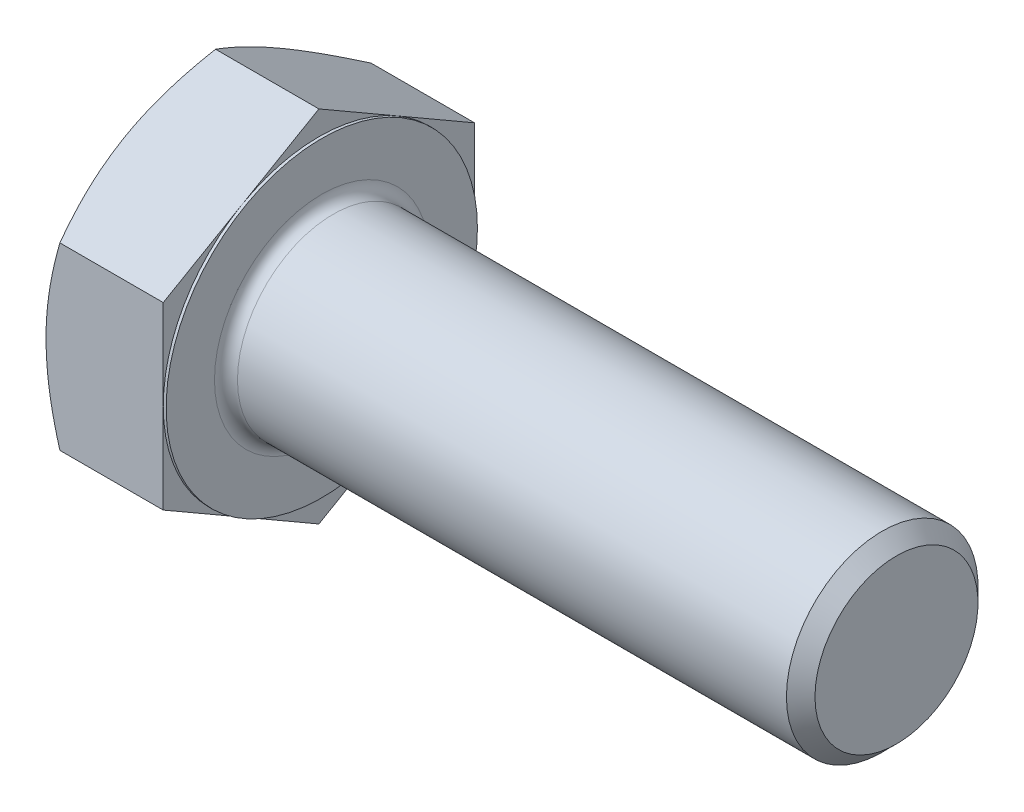
SolidWorks part; units mm, degrees
extrude "BaseHead" add sketch "Sketch1" along normal blind 15.9258
sketch "Sketch1" plane through (0, 0, 0) normal (1, 0, 0) x (0, 0, -1)
  line L0 (20.6375, 11.9151) -> (20.6375, -11.9151)
  line L1 (-20.6375, 11.9151) -> (-20.6375, -11.9151)
  line L2 (20.6375, -11.9151) -> (0, -23.8301)
  line L3 (0, -23.8301) -> (-20.6375, -11.9151)
  line L4 (20.6375, 11.9151) -> (0, 23.8301)
  line L5 (0, 23.8301) -> (-20.6375, 11.9151)
  dimension "D2" = 120
  dimension "D3" = 20.6375
  dimension "D4" = 20.6375
  dimension "D5" = 20.6375
revolve "HeadChamfer" cut sketch "Sketch3" angle 360 about L6 other way angle 60
sketch "Sketch3" plane through (0, 0, 0) normal (0, 0, 1) x (1, 0, 0)
  line L0 (0, 20.6375) -> (5.5094, 30.1801)
  line L1 (0, 23.8301) -> (0, 11.9151) construction
  line L2 (5.5094, 30.1801) -> (5.5094, 36.5301)
  line L3 (5.5094, 36.5301) -> (-12.7, 36.5301)
  line L4 (-12.7, 36.5301) -> (-12.7, 20.6375)
  line L5 (-12.7, 20.6375) -> (0, 20.6375)
  line L6 (0, 0) -> (99.06, 0) construction
  line L7 (15.9258, 23.8301) -> (0, 23.8301) construction
  dimension "D1" = 20.6375
  dimension "D2" = 6.35
  dimension "D3" = 12.7
  dimension "D4" = 6.35
  dimension "Head_ch_ang" = 30
ref_plane "Plane1" through (0, 0, 0) normal (0, 0, 1) x (1, 0, 0)
ref_plane "Plane2" through (0, 0, 0) normal (0, 1, 0) x (1, 0, 0)
ref_plane "Plane3" through (0, 0, 0) normal (1, 0, 0) x (0, 0, -1)
sketch "BodySke" plane through (0, 0, 0) normal (0, 0, 1) x (1, 0, 0)
  line L0 (0, 11.9151) -> (0, -11.9151) construction
  line L1 (0, 0) -> (92.1258, 0)
  line L2 (0, 0) -> (0, 12.7)
  line L3 (0, 12.7) -> (90.2335, 12.7)
  line L4 (92.1258, 0) -> (92.1258, 10.8077)
  line L5 (15.9258, 23.8301) -> (15.9258, 11.9151) construction
  line L6 (92.1258, 10.8077) -> (90.2335, 12.7)
  line L7 (0, 0) -> (96.52, 0) construction
  line L8 (92.1258, -10.8077) -> (90.2335, -12.7) construction
  line L9 (0, -12.7) -> (90.2335, -12.7) construction
  line L10 (18.034, 15.24) -> (18.034, -1.27) construction
  line L11 (60.3758, 15.24) -> (60.3758, -1.27) construction
  line L12 (15.9258, 11.9151) -> (15.9258, -11.9151) construction
  dimension "Diameter" = 25.4
revolve "BaseBody" add sketch "BodySke" angle 360 about L7
cosmetic thread "ThreadCosmetic" [suppressed] parameters "Thread_length"=31.75, "Thread_minor"=21.6154
sketch "Sketch4" plane through (0, 0, 0) normal (0, 0, 1) x (1, 0, 0)
  line L1 (15.9258, 23.8301) -> (15.9258, 11.9151) construction
  line L2 (15.9258, 20.6375) -> (15.5448, 20.6375)
  line L3 (15.9258, 20.6375) -> (15.9258, 49.2301)
  line L4 (15.9258, 49.2301) -> (15.5448, 49.2301)
  line L5 (0, 0) -> (95.25, 0) construction
  line L6 (0, 0) -> (96.52, 0) construction
  line L7 (15.5448, 20.6375) -> (15.5448, 49.2301)
  line L8 (15.9258, 23.8301) -> (1.8433, 23.8301) construction
  dimension "D1" = 20.6375
  dimension "D2" = 25.4
revolve "BearingFace" cut sketch "Sketch4" angle 360 about L5
fillet "HeadFillet" radius 1.524 1 edges at (15.9258, 0, -12.7)
sketch "ThdSchSke" plane through (0, 0, 0) normal (0, 0, 1) x (1, 0, 0)
  line L0 (60.3758, -10.8077) -> (59.0508, -12.7)
  line L1 (60.3758, -10.8077) -> (61.7008, -12.7)
  line L2 (61.7008, -12.7) -> (61.7008, -15.875)
  line L3 (-3.175, 0) -> (5.1513, 0) construction
  line L5 (61.7008, -15.875) -> (59.0508, -15.875)
  line L6 (59.0508, -15.875) -> (59.0508, -12.7)
  dimension "Thread_minor" = 21.6154
  dimension "Diameter" = 25.4
  dimension "Start" = 60.3758
revolve "ThreadSchematic" [suppressed] cut sketch "ThdSchSke" angle 360 about L3
pattern_linear "ThdSchPat" [suppressed]
equation "\"D3@Sketch1\" = \"Width_flats@Sketch1\" / 2"
equation "\"D4@Sketch1\" = \"D3@Sketch1\""
equation "\"D5@Sketch1\" = \"D4@Sketch1\""
equation "\"Thread_minor@ThreadCosmetic\" = \"Minor_dia@BodySke\""
equation "\"D1@Sketch3\" = \"Width_flats@Sketch1\" / 2"
equation "\"D1@Sketch4\" = \"Width_flats@Sketch1\" / 2"
equation "\"Thread_length@ThreadCosmetic\" = ((sgn( (\"Length@BodySke\" - \"Advance@BodySke\" ) - \"Thread_nom@BodySke\" )-1)*( (\"Length@BodySke\" - \"Advance@BodySke\" ) - \"Thread_nom@BodySke\" ))/-2+ \"Thread_nom@BodySke\""
equation "\"Thread_minor@ThdSchSke\" = \"Minor_dia@BodySke\""
equation "\"Diameter@ThdSchSke\" = \"Diameter@BodySke\""
equation "\"Overcut@ThdSchSke\" = \"Diameter@BodySke\" * 1.25"
equation "\"Start@ThdSchSke\" = \"Head_ht@BaseHead\" + \"Length@BodySke\" - \"Thread_length@ThreadCosmetic\"  '---Non-countersunk---"
equation "\"Num_threads@ThdSchPat\" = int( \"Thread_length@ThreadCosmetic\" / \"Advance@BodySke\" + 0.999 )  + 1"
equation "\"Advance@ThdSchPat\" = \"Thread_length@ThreadCosmetic\" /  (\"Num_threads@ThdSchPat\" - 1) 'relax it"
equation "\"Num_threads@ThdSchPat\" = \"Num_threads@ThdSchPat\" - sgn( \"Num_threads@ThdSchPat\" - 1) '---chamfered tips only---"
